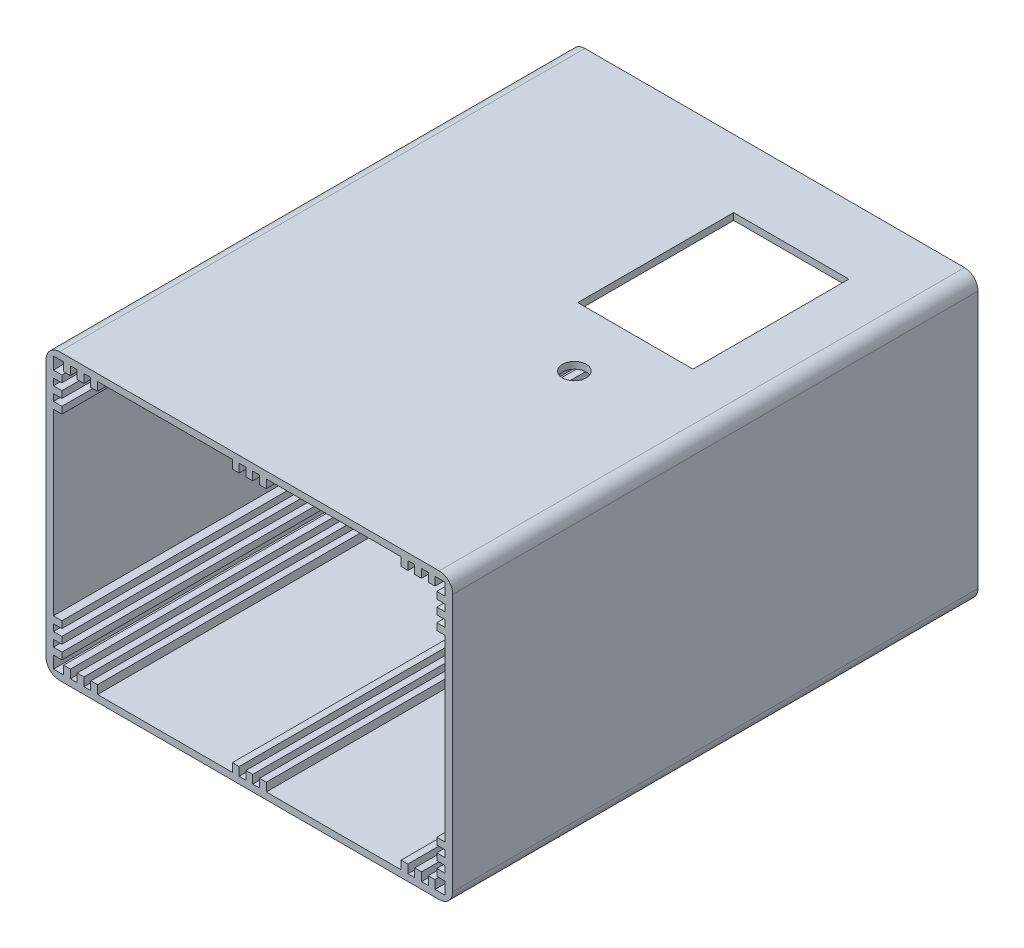
SolidWorks part; units mm, degrees
ref_plane "Front Plane" through (0, 0, 0) normal (0, 0, 1) x (1, 0, 0)
ref_plane "Top Plane" through (0, 0, 0) normal (0, 1, 0) x (1, 0, 0)
ref_plane "Right Plane" through (0, 0, 0) normal (1, 0, 0) x (0, 0, -1)
sketch "Sketch1" plane through (0, 0, 0) normal (0, 0, 1) x (1, 0, 0)
  line L1 (-60, -42) -> (60, -42)
  line L2 (-60, -42) -> (-60, 42)
  line L3 (-60, 42) -> (60, 42)
  line L4 (60, -42) -> (60, 42)
  line L5 (-60, -42) -> (60, 42) construction
  line L6 (-60, 42) -> (60, -42) construction
  line L7 (-57.8, -40) -> (57.8, -40)
  line L8 (-57.8, -40) -> (-57.8, 40)
  line L9 (-57.8, 40) -> (57.8, 40)
  line L10 (57.8, -40) -> (57.8, 40)
  line L11 (-57.8, -40) -> (57.8, 40) construction
  line L12 (-57.8, 40) -> (57.8, -40) construction
  point P0 (0, 0)
  point P6 (0, 0)
  dimension "D1" = 120
  dimension "D2" = 84
  dimension "D3" = 2
  dimension "D4" = 2.2
extrude "Boss-Extrude1" add sketch "Sketch1" along normal blind 155
fillet "Fillet1" radius 4 4 edges at (-60, -42, 77.5) (60, -42, 77.5) (60, 42, 77.5) (-60, 42, 77.5)
sketch "Sketch3" plane through (0, 0, 155) normal (0, 0, 1) x (1, 0, 0)
  line L0 (57.8, 40) -> (-57.8, 40) construction
  line L1 (-54.8, 40) -> (-52.8, 40)
  line L2 (-54.8, 40) -> (-54.8, 37.5)
  line L3 (-54.8, 37.5) -> (-52.8, 37.5)
  line L4 (-52.8, 40) -> (-52.8, 37.5)
  line L5 (-60, 38) -> (-60, -38) construction
  line L6 (-50.8, 40) -> (-48.8, 40)
  line L7 (-50.8, 40) -> (-50.8, 37.5)
  line L8 (-50.8, 37.5) -> (-48.8, 37.5)
  line L9 (-48.8, 40) -> (-48.8, 37.5)
  line L10 (-46.8, 40) -> (-44.8, 40)
  line L11 (-46.8, 40) -> (-46.8, 37.5)
  line L12 (-46.8, 37.5) -> (-44.8, 37.5)
  line L13 (-44.8, 40) -> (-44.8, 37.5)
  line L14 (-57.8, 40) -> (-57.8, -40) construction
  line L15 (-57.8, 36.4) -> (-55.3, 36.4)
  line L16 (-57.8, 36.4) -> (-57.8, 34.4)
  line L17 (-57.8, 34.4) -> (-55.3, 34.4)
  line L18 (-55.3, 36.4) -> (-55.3, 34.4)
  line L19 (56, 42) -> (-56, 42) construction
  line L20 (-57.8, 32.4) -> (-55.3, 32.4)
  line L21 (-57.8, 32.4) -> (-57.8, 30.4)
  line L22 (-57.8, 30.4) -> (-55.3, 30.4)
  line L23 (-55.3, 32.4) -> (-55.3, 30.4)
  line L24 (-57.8, 28.4) -> (-55.3, 28.4)
  line L25 (-57.8, 28.4) -> (-57.8, 26.4)
  line L26 (-57.8, 26.4) -> (-55.3, 26.4)
  line L27 (-55.3, 28.4) -> (-55.3, 26.4)
  line L28 (0, 40) -> (0, -40) construction
  line L29 (-57.8, -40) -> (57.8, -40) construction
  line L30 (-57.8, 0) -> (57.8, 0) construction
  line L31 (57.8, -40) -> (57.8, 40) construction
  line L32 (57.8, 26.4) -> (55.3, 26.4)
  line L33 (55.3, 28.4) -> (55.3, 26.4)
  line L34 (57.8, 28.4) -> (55.3, 28.4)
  line L35 (57.8, 28.4) -> (57.8, 26.4)
  line L36 (57.8, 30.4) -> (55.3, 30.4)
  line L37 (55.3, 32.4) -> (55.3, 30.4)
  line L38 (57.8, 32.4) -> (55.3, 32.4)
  line L39 (57.8, 32.4) -> (57.8, 30.4)
  line L40 (57.8, 34.4) -> (55.3, 34.4)
  line L41 (55.3, 36.4) -> (55.3, 34.4)
  line L42 (57.8, 36.4) -> (55.3, 36.4)
  line L43 (57.8, 36.4) -> (57.8, 34.4)
  line L44 (54.8, 37.5) -> (52.8, 37.5)
  line L45 (52.8, 40) -> (52.8, 37.5)
  line L46 (54.8, 40) -> (52.8, 40)
  line L47 (54.8, 40) -> (54.8, 37.5)
  line L48 (50.8, 37.5) -> (48.8, 37.5)
  line L49 (48.8, 40) -> (48.8, 37.5)
  line L50 (50.8, 40) -> (48.8, 40)
  line L51 (50.8, 40) -> (50.8, 37.5)
  line L52 (46.8, 37.5) -> (44.8, 37.5)
  line L53 (44.8, 40) -> (44.8, 37.5)
  line L54 (46.8, 40) -> (44.8, 40)
  line L55 (46.8, 40) -> (46.8, 37.5)
  line L56 (46.8, -40) -> (46.8, -37.5)
  line L57 (46.8, -40) -> (44.8, -40)
  line L58 (44.8, -40) -> (44.8, -37.5)
  line L59 (46.8, -37.5) -> (44.8, -37.5)
  line L60 (50.8, -40) -> (50.8, -37.5)
  line L61 (50.8, -40) -> (48.8, -40)
  line L62 (48.8, -40) -> (48.8, -37.5)
  line L63 (50.8, -37.5) -> (48.8, -37.5)
  line L64 (54.8, -40) -> (54.8, -37.5)
  line L65 (54.8, -40) -> (52.8, -40)
  line L66 (52.8, -40) -> (52.8, -37.5)
  line L67 (54.8, -37.5) -> (52.8, -37.5)
  line L68 (57.8, -36.4) -> (57.8, -34.4)
  line L69 (57.8, -36.4) -> (55.3, -36.4)
  line L70 (55.3, -36.4) -> (55.3, -34.4)
  line L71 (57.8, -34.4) -> (55.3, -34.4)
  line L72 (57.8, -32.4) -> (57.8, -30.4)
  line L73 (57.8, -32.4) -> (55.3, -32.4)
  line L74 (55.3, -32.4) -> (55.3, -30.4)
  line L75 (57.8, -30.4) -> (55.3, -30.4)
  line L76 (57.8, -28.4) -> (57.8, -26.4)
  line L77 (57.8, -28.4) -> (55.3, -28.4)
  line L78 (55.3, -28.4) -> (55.3, -26.4)
  line L79 (57.8, -26.4) -> (55.3, -26.4)
  line L80 (-46.8, -37.5) -> (-44.8, -37.5)
  line L81 (-44.8, -40) -> (-44.8, -37.5)
  line L82 (-46.8, -40) -> (-44.8, -40)
  line L83 (-46.8, -40) -> (-46.8, -37.5)
  line L84 (-50.8, -37.5) -> (-48.8, -37.5)
  line L85 (-48.8, -40) -> (-48.8, -37.5)
  line L86 (-50.8, -40) -> (-48.8, -40)
  line L87 (-50.8, -40) -> (-50.8, -37.5)
  line L88 (-54.8, -37.5) -> (-52.8, -37.5)
  line L89 (-52.8, -40) -> (-52.8, -37.5)
  line L90 (-54.8, -40) -> (-52.8, -40)
  line L91 (-54.8, -40) -> (-54.8, -37.5)
  line L92 (-57.8, -34.4) -> (-55.3, -34.4)
  line L93 (-55.3, -36.4) -> (-55.3, -34.4)
  line L94 (-57.8, -36.4) -> (-55.3, -36.4)
  line L95 (-57.8, -36.4) -> (-57.8, -34.4)
  line L96 (-57.8, -30.4) -> (-55.3, -30.4)
  line L97 (-55.3, -32.4) -> (-55.3, -30.4)
  line L98 (-57.8, -32.4) -> (-55.3, -32.4)
  line L99 (-57.8, -32.4) -> (-57.8, -30.4)
  line L100 (-57.8, -26.4) -> (-55.3, -26.4)
  line L101 (-55.3, -28.4) -> (-55.3, -26.4)
  line L102 (-57.8, -28.4) -> (-55.3, -28.4)
  line L103 (-57.8, -28.4) -> (-57.8, -26.4)
  line L104 (-5, -37.5) -> (-3, -37.5)
  line L105 (-5, 40) -> (-3, 40)
  line L106 (-5, 40) -> (-5, 37.5)
  line L107 (-5, 37.5) -> (-3, 37.5)
  line L108 (-3, 40) -> (-3, 37.5)
  line L109 (-1, 40) -> (1, 40)
  line L110 (-1, 40) -> (-1, 37.5)
  line L111 (-1, 37.5) -> (1, 37.5)
  line L112 (1, 40) -> (1, 37.5)
  line L113 (3, 40) -> (5, 40)
  line L114 (3, 40) -> (3, 37.5)
  line L115 (3, 37.5) -> (5, 37.5)
  line L116 (5, 40) -> (5, 37.5)
  line L117 (-3, -40) -> (-3, -37.5)
  line L118 (-5, -40) -> (-3, -40)
  line L119 (-5, -40) -> (-5, -37.5)
  line L120 (-1, -37.5) -> (1, -37.5)
  line L121 (1, -40) -> (1, -37.5)
  line L122 (-1, -40) -> (1, -40)
  line L123 (-1, -40) -> (-1, -37.5)
  line L124 (3, -37.5) -> (5, -37.5)
  line L125 (5, -40) -> (5, -37.5)
  line L126 (3, -40) -> (5, -40)
  line L127 (3, -40) -> (3, -37.5)
  point P124 (0, 37.5)
  point P125 (3, 38.75)
  dimension "D1" = 2
  dimension "D2" = 2.5
  dimension "D3" = 2
  dimension "D4" = 2
  dimension "D5" = 15.2
  dimension "D6" = 2
  dimension "D7" = 2.5
  dimension "D8" = 2
  dimension "D9" = 2
  dimension "D10" = 15.6
  dimension "D11" = 2
  dimension "D12" = 2
  dimension "D13" = 2
  dimension "D14" = 2.5
extrude "FinalBox" add sketch "Sketch3" against normal through all
sketch "Sketch5" plane through (0, 40, 0) normal (0, -1, 0) x (1, 0, 0)
  line L0 (44.8, 0) -> (5, 0) construction
  line L1 (7.9, 20) -> (41.9, 20)
  line L2 (7.9, 20) -> (7.9, 66)
  line L3 (7.9, 66) -> (41.9, 66)
  line L4 (41.9, 20) -> (41.9, 66)
  line L5 (5, 0) -> (5, 155) construction
  line L6 (44.8, 0) -> (44.8, 155) construction
  dimension "D1" = 34
  dimension "D2" = 46
  dimension "D3" = 20
  dimension "D4" = 2.9
  dimension "D5" = 2.9
extrude "TFT" cut sketch "Sketch5" against normal through all
sketch "Sketch6" plane through (0, 42, 0) normal (0, 1, 0) x (1, 0, 0)
  line L0 (41.9, -66) -> (7.9, -66) construction
  circle A0 centre (24.9, -84) radius 3.5
  point P4 (0, 0)
  point P5 (24.9, -66)
  dimension "D1" = 7
  dimension "D2" = 18
extrude "Encoder" cut sketch "Sketch6" against normal blind 10
